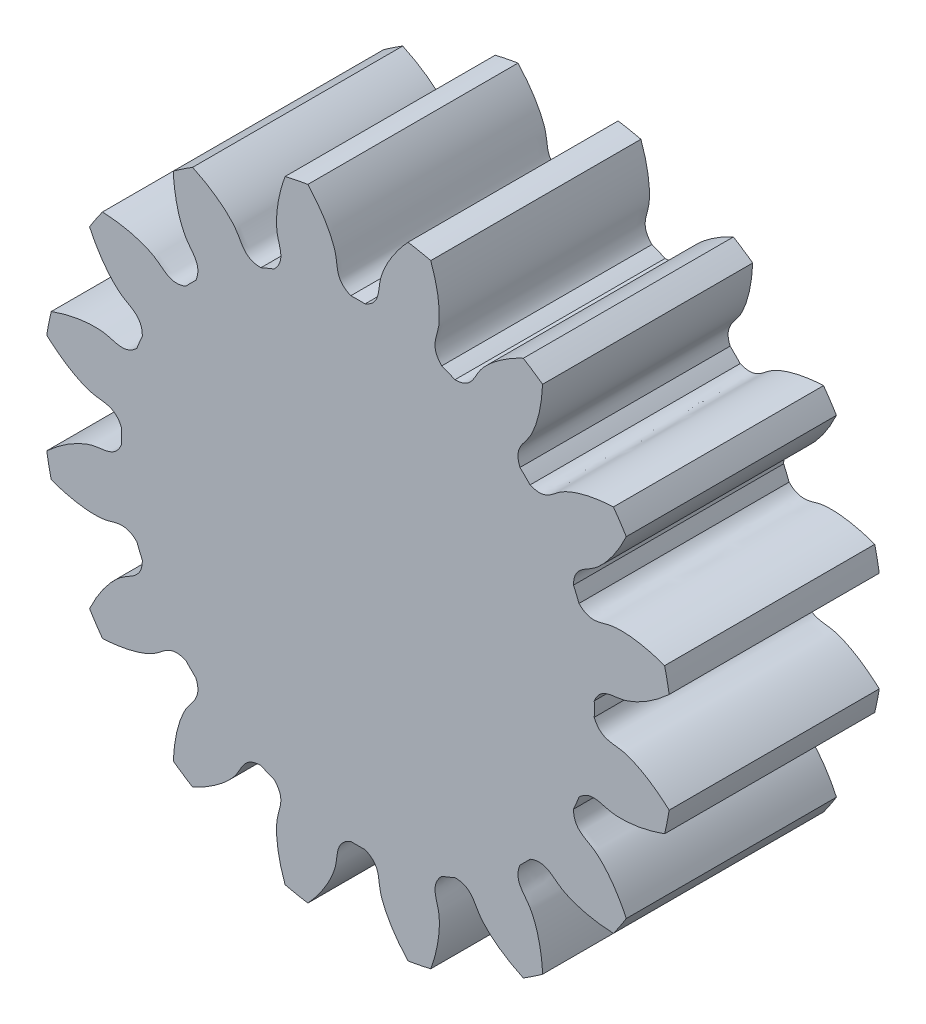
SolidWorks part; units mm, degrees
ref_plane "前视基准面" through (0, 0, 0) normal (0, 0, 1) x (1, 0, 0)
ref_plane "上视基准面" through (0, 0, 0) normal (0, 1, 0) x (1, 0, 0)
ref_plane "右视基准面" through (0, 0, 0) normal (1, 0, 0) x (0, 0, -1)
other "Configuration Table"
sketch "草图1" plane through (0, 0, 0) normal (0, 0, 1) x (1, 0, 0)
  circle A0 centre (0, 0) radius 4.5
extrude "凸台-拉伸1" add sketch "草图1" along normal blind 3
ref_axis "基准轴1" through (0, 0, 3) along (0, 0, -1)
sketch "草图2" plane through (0, 0, 0) normal (0, 0, 1) x (1, 0, 0)
  line L0 (0, 0) -> (0, 4.5) construction
  circle A0 centre (0, 0) radius 4.5 construction
  arc A1 (0.1017, 3.3735) -> (-0.1017, 3.3735) centre (0, 0) ccw
  arc A2 (1.5609, 5.0814) -> (-1.5609, 5.0814) centre (0, 0) ccw
  spline S0 degree 3 poles (0.1017, 3.3735) (0.3209, 3.4651) (0.2847, 3.6353) (0.3224, 3.7934) (0.3256, 3.8058) (0.3295, 3.8195) (0.334, 3.8346) (0.3394, 3.8511) (0.3455, 3.8688) (0.3526, 3.8879) (0.3605, 3.9082) (0.3695, 3.9297) (0.3794, 3.9524) (0.3905, 3.9763) (0.4027, 4.0013) (0.4161, 4.0274) (0.4307, 4.0545) (0.4466, 4.0827) (0.4638, 4.1118) (0.4823, 4.1419) (0.5023, 4.1728) (0.5238, 4.2046) (0.5467, 4.2372) (0.5712, 4.2705) (0.5973, 4.3045) (0.6249, 4.3392) (0.6543, 4.3744) (0.6853, 4.4102) (0.718, 4.4465) (0.7524, 4.4833) (0.7887, 4.5204) (0.8267, 4.5578) (0.8666, 4.5955) (0.9084, 4.6334) (0.952, 4.6715) (0.9975, 4.7096) (1.045, 4.7478) (1.0944, 4.7859) (1.1457, 4.8239) (1.1991, 4.8618) (1.2544, 4.8994) (1.3117, 4.9367) (1.3711, 4.9737) (1.4537, 5.023) (1.5175, 5.0584) (1.5609, 5.0814) knots 0 0 0 0 0.200958 0.205848 0.21139 0.217584 0.224431 0.231929 0.240079 0.248881 0.258335 0.268441 0.2792 0.29061 0.302672 0.315386 0.328753 0.342771 0.357441 0.372764 0.388738 0.405364 0.422643 0.440573 0.459155 0.47839 0.498276 0.518814 0.540005 0.561847 0.584342 0.607488 0.631287 0.655737 0.68084 0.706594 0.733001 0.760059 0.78777 0.816132 0.845147 0.874814 0.905132 0.936103 1 1 1 1
  spline S1 degree 3 poles (-0.1017, 3.3735) (-0.3209, 3.4651) (-0.2847, 3.6353) (-0.3224, 3.7934) (-0.3256, 3.8058) (-0.3295, 3.8195) (-0.334, 3.8346) (-0.3394, 3.8511) (-0.3455, 3.8688) (-0.3526, 3.8879) (-0.3605, 3.9082) (-0.3695, 3.9297) (-0.3794, 3.9524) (-0.3905, 3.9763) (-0.4027, 4.0013) (-0.4161, 4.0274) (-0.4307, 4.0545) (-0.4466, 4.0827) (-0.4638, 4.1118) (-0.4823, 4.1419) (-0.5023, 4.1728) (-0.5238, 4.2046) (-0.5467, 4.2372) (-0.5712, 4.2705) (-0.5973, 4.3045) (-0.6249, 4.3392) (-0.6543, 4.3744) (-0.6853, 4.4102) (-0.718, 4.4465) (-0.7524, 4.4833) (-0.7887, 4.5204) (-0.8267, 4.5578) (-0.8666, 4.5955) (-0.9084, 4.6334) (-0.952, 4.6715) (-0.9975, 4.7096) (-1.045, 4.7478) (-1.0944, 4.7859) (-1.1457, 4.8239) (-1.1991, 4.8618) (-1.2544, 4.8994) (-1.3117, 4.9367) (-1.3711, 4.9737) (-1.4537, 5.023) (-1.5175, 5.0584) (-1.5609, 5.0814) knots 0 0 0 0 0.200958 0.205848 0.21139 0.217584 0.224431 0.231929 0.240079 0.248881 0.258335 0.268441 0.2792 0.29061 0.302672 0.315386 0.328753 0.342771 0.357441 0.372764 0.388738 0.405364 0.422643 0.440573 0.459155 0.47839 0.498276 0.518814 0.540005 0.561847 0.584342 0.607488 0.631287 0.655737 0.68084 0.706594 0.733001 0.760059 0.78777 0.816132 0.845147 0.874814 0.905132 0.936103 1 1 1 1
extrude "切除-拉伸1" cut sketch "草图2" along normal through all
pattern_circular "阵列(圆周)1" count 16 every 22.5 about axis through (0, 0, 3) along (0, 0, -1) of "切除-拉伸1"
sketch "草图3" plane through (0, 0, 0) normal (0, 0, 1) x (1, 0, 0)
  circle A0 centre (0, 0) radius 4 construction
  dimension "Dn" = 8
